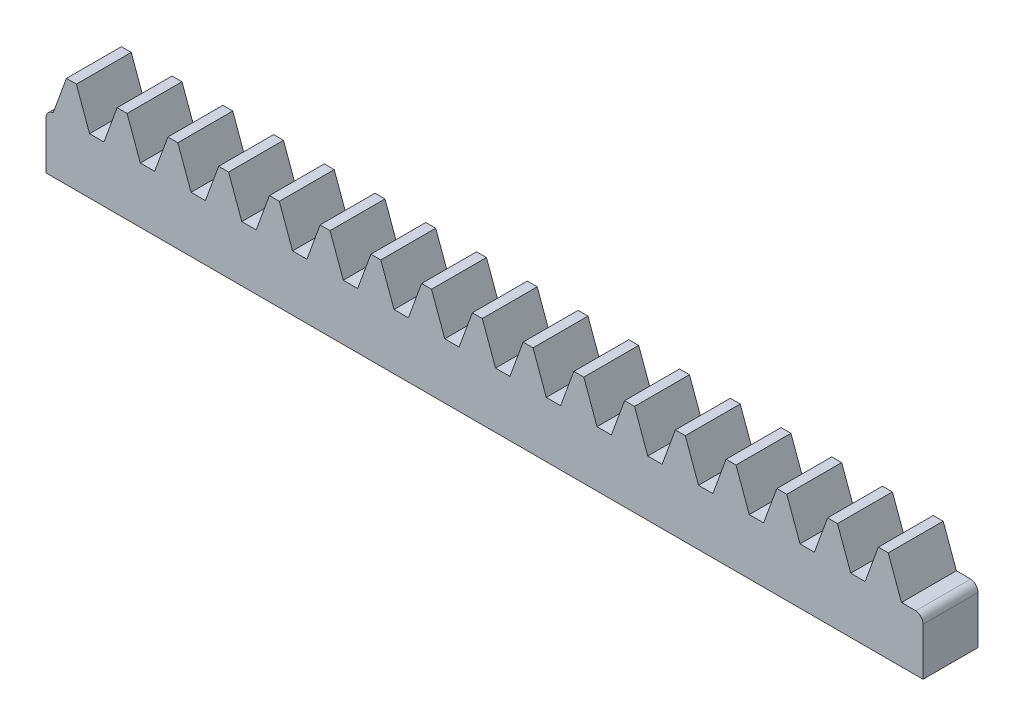
SolidWorks part; units mm, degrees
extrude "Blank" add sketch "BlankSke" against normal blind 3.4
sketch "BlankSke" plane through (0, 0, 0) normal (0, 0, 1) x (1, 0, 0)
  line L1 (0, 0) -> (54.3, 0)
  line L2 (0, 0) -> (0, 5.7)
  line L3 (0, 5.7) -> (54.3, 5.7)
  line L4 (54.3, 0) -> (54.3, 5.7)
  dimension "Length" = 54.3
ref_plane "Plane1" through (0, 0, 0) normal (0, 0, 1) x (1, 0, 0)
ref_plane "Plane2" through (0, 0, 0) normal (0, 1, 0) x (1, 0, 0)
ref_plane "Plane3" through (0, 0, 0) normal (1, 0, 0) x (0, 0, -1)
sketch "HoldingSke" plane through (0, 0, 0) normal (0, 1, 0) x (1, 0, 0)
  line L0 (0, 0) -> (0.1392, 0.9903)
  line L1 (-15, 0) -> (100, 0) construction
  line L2 (0, 0) -> (-2.1039, 2.3779)
  line L3 (0, 0) -> (-11.863, 4.5341)
  line L4 (0, 0) -> (8.1655, 2.8116)
  line L5 (0, 0) -> (-23.7986, -8.8762)
  line L6 (0, 0) -> (-10.5278, -7.1032)
  line L9 (-71.009, 38.7566) -> (-19.9837, 57.3283)
  line L10 (-76.2, 3.3779) -> (-71.5, 3.3779)
  line L11 (0, 0) -> (-3.4, 0)
  line L12 (-76.2, 101.6) -> (-76.162, 101.6)
  line L13 (24.9733, 27.94) -> (52.9518, 28.4284)
  line L14 (24.9733, 27.94) -> (24.9743, 27.94)
  line L15 (24.9733, 27.94) -> (100.4006, 29.5858)
  circle A0 centre (0, 0) radius 19.05
  circle A1 centre (0, 0) radius 2.35
  circle A2 centre (0, 0) radius 12.7
  dimension "Num_teeth" = 19
  dimension "Width" = 3.4
  dimension "Length" = 54.3
  dimension "Pitch_height" = 4.7
sketch "TooCutSkeIll" plane through (0, 0, 0) normal (0, 0, 1) x (1, 0, 0)
  line L0 (-1.2538, 5.6737) -> (-0.5045, 3.6152)
  line L1 (-0.2687, 3.45) -> (0.2687, 3.45)
  line L2 (0.5045, 3.6152) -> (1.2538, 5.6737)
  line L3 (54.3, 5.7) -> (0, 5.7) construction
  line L4 (0, 0) -> (0, 64.897) construction
  line L5 (-13.208, 4.7) -> (12.954, 4.7) construction
  line L6 (0, 0) -> (54.3, 0) construction
  line L7 (0.8994, 4.7) -> (0.8994, 48.7463) construction
  line L8 (-0.8994, 4.7) -> (-0.8994, 48.7463) construction
  line L9 (1.2914, 5.7) -> (1.2914, 5.7254)
  line L10 (-1.2914, 5.7) -> (-1.2914, 5.7254)
  line L11 (-1.2914, 5.7254) -> (1.2914, 5.7254)
  arc A0 (0.2687, 3.45) -> (0.5045, 3.6152) centre (0.2687, 3.701) ccw
  arc A1 (-0.5045, 3.6152) -> (-0.2687, 3.45) centre (-0.2687, 3.701) ccw
  arc A2 (1.2914, 5.7) -> (1.2538, 5.6737) centre (1.2914, 5.66) ccw
  arc A3 (-1.2538, 5.6737) -> (-1.2914, 5.7) centre (-1.2914, 5.66) ccw
  dimension "Addendum_plus" = 1.0254
  dimension "Pitch_height" = 4.7
  dimension "Pressure_angle" = 20
  dimension "Gap_width" = 1.7988
  dimension "Dedendum" = 1.25
extrude "ToothCutIll" [suppressed] cut sketch "TooCutSkeIll" against normal through all
sketch "TooCutSkeSim" plane through (0, 0, 0) normal (0, 0, 1) x (1, 0, 0)
  line L0 (0.4444, 3.45) -> (-0.4444, 3.45)
  line L1 (1.2726, 5.7254) -> (0.4444, 3.45)
  line L2 (0, 17.4625) -> (0, 53.467) construction
  line L3 (1.2726, 5.7254) -> (-1.2726, 5.7254)
  line L6 (-1.2726, 5.7254) -> (-0.4444, 3.45)
  line L9 (-0.8994, 4.7) -> (0.8994, 4.7) construction
  line L10 (0, 0) -> (54.3, 0) construction
  line L11 (0.8994, 4.7) -> (0.8994, 53.467) construction
  line L12 (-0.8994, 4.7) -> (-0.8994, 53.467) construction
  dimension "Addendum_plus" = 1.0254
  dimension "Pitch_height" = 4.7
  dimension "Pressure_angle" = 20
  dimension "Gap_width" = 1.7988
  dimension "Dedendum" = 1.25
extrude "ToothCutSim" cut sketch "TooCutSkeSim" against normal through all
pattern_linear "TeethCuts" count 19 spacing 3.1416 along (1, 0, 0) of "ToothCutIll", "ToothCutSim"
fillet "Verrundung1" radius 0.5 1 edges at (54.3, 4.6822, -1.7)
fillet "Verrundung2" radius 0.5 1 edges at (0, 3.45, -1.7)
scale "Scale1" scale about origin uniform scaling yes scale factor 1.46
equation "' \"Module@HoldingSke\" = 6.35"
equation "' \"Num_teeth@HoldingSke\" = 12"
equation "' \"Ap@HoldingSke\" =  20"
equation "' \"Ap@HoldingSke\" = 20"
equation "' \"Width@HoldingSke\" = 0.25 * 25.4"
equation "' \"Show_teeth@HoldingSke\" = 500"
equation "' \"Backlash@HoldingSke\" = 0.009 * 25.4"
equation "' \"Addendum_fac@HoldingSke\" = 1.0"
equation "' \"Dedendum_fac@HoldingSke\" = 1.25"
equation "' \"Dedendum_add@HoldingSke\" = 0.00005 * 25.4"
equation "' \"Clearance_fac@HoldingSke\" = 0.25"
equation "' \"Pitch_height@HoldingSke\" = 1 * 25.4"
equation "' \"Length@HoldingSke\" = 4.71 * 25.4"
equation "\"Pitch@HoldingSke\" = 1 / \"Module@HoldingSke\""
equation "\"MPH@HoldingSke\" = \"Dedendum_fac@HoldingSke\" / \"Pitch@HoldingSke\" + 2 * \"Dedendum_add@HoldingSke\" + 0.002 * 25.4"
equation "\"MPH@HoldingSke\" = ((sgn( \"MPH@HoldingSke\" - \"Pitch_height@HoldingSke\")+1)*( \"MPH@HoldingSke\" - \"Pitch_height@HoldingSke\"))/2 + \"Pitch_height@HoldingSke\""
equation "\"Blank_height@BlankSke\" = \"Pitch_height@HoldingSke\" + \"Addendum_fac@HoldingSke\"  / \"Pitch@HoldingSke\" "
equation "\"Length@BlankSke\" =  \"Length@HoldingSke\""
equation "\"Face_width@Blank\" = \"Width@HoldingSke\""
equation "\"Pressure_angle@TooCutSkeIll\" = \"Ap@HoldingSke\""
equation "\"Addendum_plus@TooCutSkeIll\" =  \"Addendum_fac@HoldingSke\"  / \"Pitch@HoldingSke\" + 0.001 *25.4"
equation "\"Dedendum@TooCutSkeIll\" = \"Dedendum_fac@HoldingSke\"  / \"Pitch@HoldingSke\""
equation "\"Pitch_height@TooCutSkeIll\" =  \"MPH@HoldingSke\""
equation "\"Gap_width@TooCutSkeIll\" = 3.14159265 / 2 / \"Pitch@HoldingSke\" + 6 * \"Backlash@HoldingSke\""
equation "\"Pressure_angle@TooCutSkeSim\" = \"Ap@HoldingSke\""
equation "\"Addendum_plus@TooCutSkeSim\" =  \"Addendum_fac@HoldingSke\"  / \"Pitch@HoldingSke\" + 0.001 * 25.4"
equation "\"Dedendum@TooCutSkeSim\" = \"Dedendum_fac@HoldingSke\"  / \"Pitch@HoldingSke\""
equation "\"Pitch_height@TooCutSkeSim\" =  \"MPH@HoldingSke\""
equation "\"Gap_width@TooCutSkeSim\" = 3.14159265 / 2 / \"Pitch@HoldingSke\" + 6 * \"Backlash@HoldingSke\""
equation "\"Root_fillet@TooCutSkeIll\" = \"Clearance_fac@HoldingSke\" / \"Pitch@HoldingSke\" + \"Dedendum_add@HoldingSke\""
equation "\"Break_rad@TooCutSkeIll\" = 0.02 / \"Pitch@HoldingSke\" * 2"
equation "\"Linear_pitch@TeethCuts\" = 3.14159265 / \"Pitch@HoldingSke\""
equation "\"Num_teeth@HoldingSke\" = int( ( \"Length@HoldingSke\" + 0 ) / (3.14159265 / \"Pitch@HoldingSke\")) + 0.9999  + 1"
equation " \"Num_teeth@TeethCuts\" = int( \"Show_teeth@HoldingSke\" ) + 1"
equation " \"Num_teeth@TeethCuts\" = ((sgn( \"Num_teeth@TeethCuts\" - \"Num_teeth@HoldingSke\" )-1)*( \"Num_teeth@TeethCuts\" - \"Num_teeth@HoldingSke\" ))/-2+ \"Num_teeth@HoldingSke\""
equation " \"Num_teeth@TeethCuts\" = ((sgn( \"Num_teeth@TeethCuts\" - 2.0)+1)*( \"Num_teeth@TeethCuts\" - 2.0))/2 +2.0"
